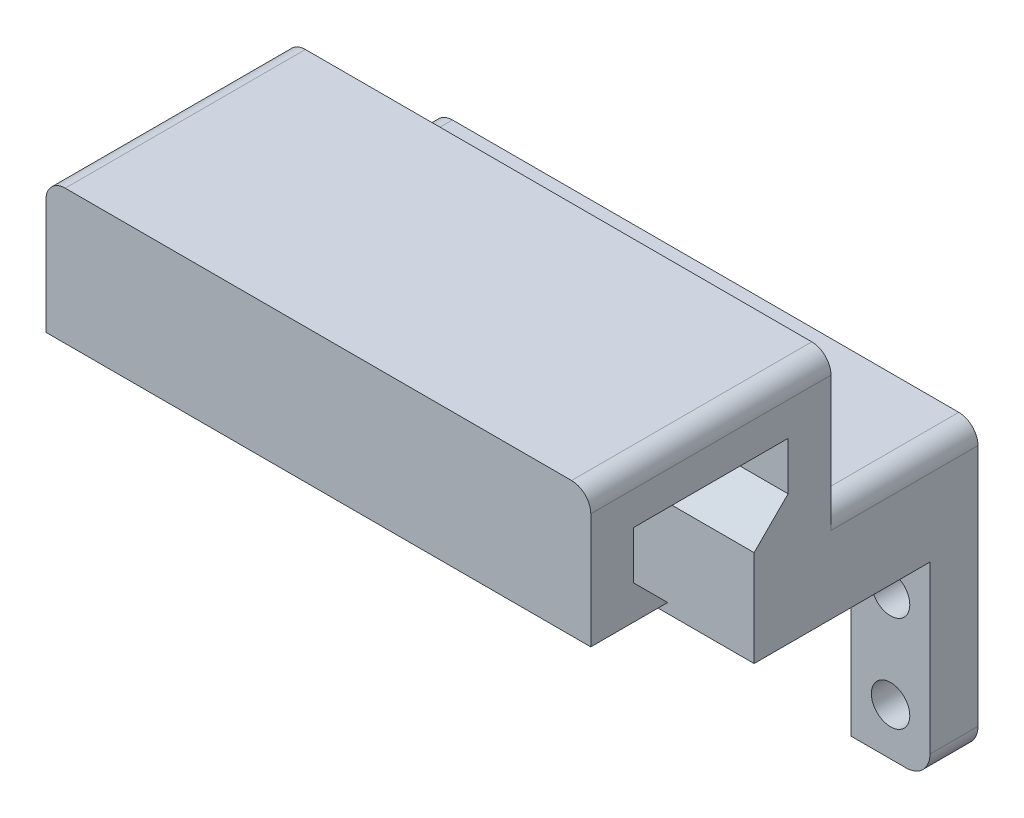
SolidWorks part; units mm, degrees
ref_plane "Alzado" through (0, 0, 0) normal (0, 0, 1) x (1, 0, 0)
ref_plane "Planta" through (0, 0, 0) normal (0, 1, 0) x (1, 0, 0)
ref_plane "Vista lateral" through (0, 0, 0) normal (1, 0, 0) x (0, 0, -1)
sketch "Sketch1" plane through (0, 0, 0) normal (0, 0, 1) x (1, 0, 0)
  line L0 (-24.25, 0) -> (24.25, 0) construction
  line L1 (24.25, -5) -> (24.25, 5) construction
  line L2 (-24.25, -5) -> (-24.25, 5) construction
  line L3 (-24.25, 5) -> (-24.25, 9.9) construction
  line L4 (-24.25, -5) -> (-20.15, -5) construction
  line L5 (-24.25, -5) -> (-24.25, -9.9) construction
  line L6 (-24.25, -5) -> (-28.35, -5) construction
  line L7 (0, -5) -> (0, 5) construction
  line L8 (-20.15, -9.9) -> (-25.85, -9.9)
  line L9 (-20.15, -9.9) -> (-20.15, 9.9)
  line L10 (-20.15, 9.9) -> (-28.35, 9.9)
  line L11 (-28.35, -7.4) -> (-28.35, 9.9)
  line L12 (20.15, 9.9) -> (28.35, 9.9)
  line L13 (28.35, -7.4) -> (28.35, 9.9)
  line L14 (20.15, -9.9) -> (25.85, -9.9)
  line L15 (20.15, -9.9) -> (20.15, 9.9)
  line L17 (-28.35, 9.9) -> (28.35, 9.9)
  line L18 (-28.35, 9.9) -> (-28.35, 17.4)
  line L19 (-25.85, 19.9) -> (25.85, 19.9)
  line L20 (28.35, 9.9) -> (28.35, 17.4)
  circle A0 centre (24.25, -5) radius 2
  circle A1 centre (-24.25, -5) radius 2
  circle A2 centre (-24.25, 5) radius 2
  circle A3 centre (24.25, 5) radius 2
  arc A4 (-28.35, 17.4) -> (-25.85, 19.9) centre (-25.85, 17.4) cw
  arc A5 (25.85, 19.9) -> (28.35, 17.4) centre (25.85, 17.4) cw
  arc A6 (28.35, -7.4) -> (25.85, -9.9) centre (25.85, -7.4) cw
  arc A7 (-25.85, -9.9) -> (-28.35, -7.4) centre (-25.85, -7.4) cw
  point P4 (0, 0)
  point P8 (24.25, 0)
  point P11 (-24.25, 0)
  point P28 (0, 0)
  point P36 (-28.35, 19.9)
  point P41 (28.35, -9.9)
  point P44 (-28.35, -9.9)
  dimension "D2" = 4
  dimension "D6" = 56.7
  dimension "D7" = 48.5
  dimension "D8" = 5
  dimension "D9" = 48.5
  dimension "D10" = 4.9
  dimension "D17" = 4.9
  dimension "D18" = 2.5
  dimension "D1" = 5
  dimension "D3" = 10
  dimension "D4" = 2
  dimension "D11" = 4.1
  dimension "D12" = 4.9
  dimension "D13" = 4.1
  dimension "D14" = 19.8
  dimension "D15" = 8.2
  dimension "D16" = 4.1
  dimension "D5" = 2
extrude "Forma básica" add sketch "Sketch1" along normal blind 5 contours A7 L8 L9 L10 L11 A1 A2 | A6 L13 L12 L15 L14 A3 A0 region at (-24.215, 0.0922, 0) region at (24.215, 0.0922, 0)
extrude "Boss-Extrude2" add sketch "Sketch1<3>" along normal blind 23.3 contours A5 L19 A4 L18 L10 L17 L12 L20 region at (0, 14.8789, 0)
sketch "Sketch1<3>" plane through (0, 0, 0) normal (0, 0, 1) x (1, 0, 0) same geometry as "Sketch1"
sketch "Sketch2" plane through (28.35, 0, 0) normal (1, 0, 0) x (0, 0, -1)
  line L0 (-23.3, 19.9) -> (-19.7645, 23.4355)
  line L1 (-23.3, 19.9) -> (0, 19.9) construction
  line L2 (-23.3, 19.9) -> (0, 19.9) construction
  line L3 (-19.7645, 23.4355) -> (-19.7645, 28.4355)
  line L4 (-19.7645, 28.4355) -> (-35.8345, 28.4355)
  line L5 (-35.8345, 28.4355) -> (-35.8345, 23.4355)
  line L6 (-35.8345, 23.4355) -> (-32.2989, 19.9)
  line L7 (-23.3, 19.9) -> (-15.3, 19.9)
  line L8 (-15.3, 19.9) -> (-15.3, 33.9)
  line L9 (-32.2989, 19.9) -> (-40.2989, 19.9)
  line L10 (-40.2989, 19.9) -> (-40.2989, 33.9)
  line L11 (-40.2989, 33.9) -> (-15.3, 33.9)
  dimension "D1" = 5
  dimension "D2" = 45
  dimension "D3" = 5
  dimension "D4" = 16.07
  dimension "D5" = 5
  dimension "D6" = 45
  dimension "D7" = 8.9989
  dimension "D8" = 8
  dimension "D9" = 14
  dimension "D10" = 8
extrude "Carril cremallera" add sketch "Sketch2" against normal up to surface (56.7 mm away) up to face at (-28.35, 6.6333, 9.4333)
sketch "Sketch3" plane through (0, 0, 23.3) normal (0, 0, 1) x (1, 0, 0)
  line L0 (-28.35, 17.4) -> (-28.35, 19.9)
  line L1 (-28.35, 19.9) -> (28.35, 19.9) construction
  line L2 (-28.35, 19.9) -> (-25.85, 19.9)
  line L3 (0, 0) -> (0, 33.9) construction
  line L4 (-28.35, 33.9) -> (28.35, 33.9) construction
  line L5 (28.35, 19.9) -> (25.85, 19.9)
  line L6 (28.35, 17.4) -> (28.35, 19.9)
  arc A0 (-25.85, 19.9) -> (-28.35, 17.4) centre (-25.85, 17.4) ccw
  arc A1 (25.85, 19.9) -> (28.35, 17.4) centre (25.85, 17.4) cw
extrude "Eliminar filete" add sketch "Sketch3" against normal up to surface (23.3 mm away) up to face at (0, 3.3333, 0)
fillet "Fillet2" radius 2 4 edges at (-28.35, 19.9, 7.65) (28.35, 19.9, 7.65) (28.35, 33.9, 27.7995) (-28.35, 33.9, 27.7995)
